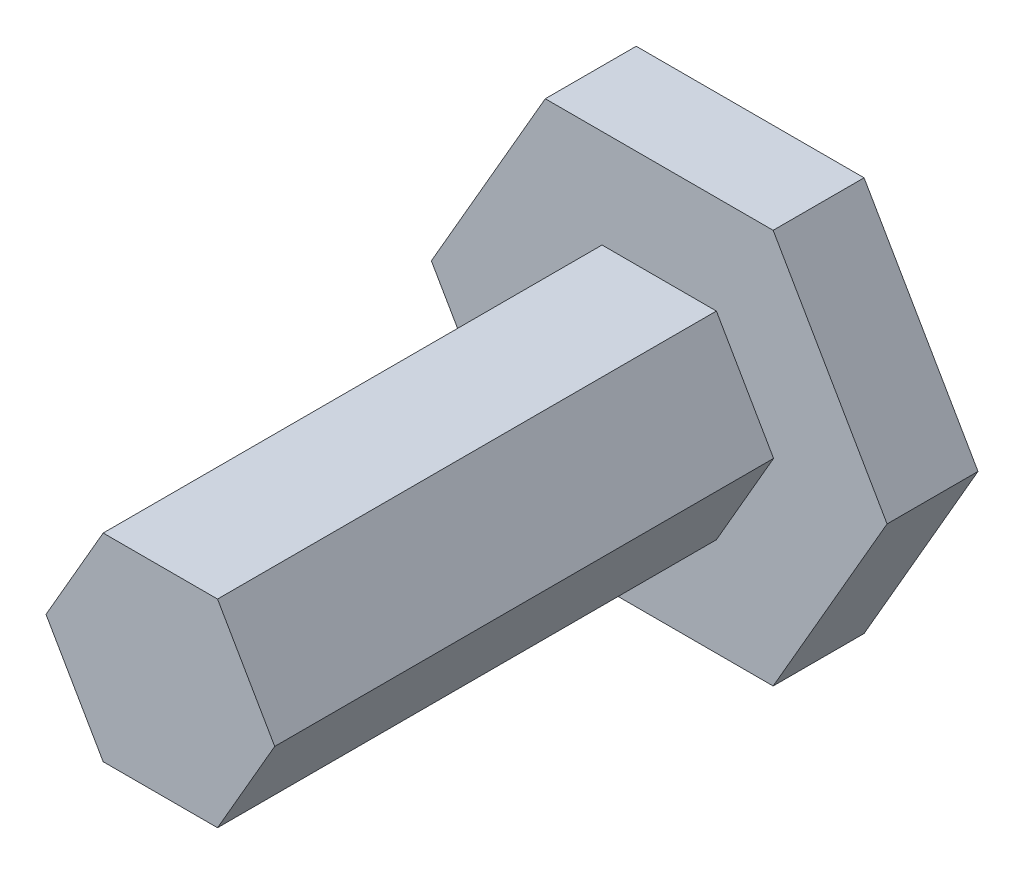
SolidWorks part; units mm, degrees
ref_plane "Front Plane" through (0, 0, 0) normal (0, 0, 1) x (1, 0, 0)
ref_plane "Top Plane" through (0, 0, 0) normal (0, 1, 0) x (1, 0, 0)
ref_plane "Right Plane" through (0, 0, 0) normal (1, 0, 0) x (0, 0, -1)
sketch "Sketch1" plane through (0, 0, 0) normal (0, 0, 1) x (1, 0, 0)
  line L0 (2.4047, -4.1651) -> (4.8094, 0)
  line L1 (1.25, -2.1651) -> (2.5, 0)
  line L2 (2.5, 0) -> (1.25, 2.1651)
  line L3 (1.25, 2.1651) -> (-1.25, 2.1651)
  line L4 (-1.25, 2.1651) -> (-2.5, 0)
  line L5 (-2.5, 0) -> (-1.25, -2.1651)
  line L6 (-1.25, -2.1651) -> (1.25, -2.1651)
  line L7 (4.8094, 0) -> (2.4047, 4.1651)
  line L8 (2.4047, 4.1651) -> (-2.4047, 4.1651)
  line L9 (-2.4047, 4.1651) -> (-4.8094, 0)
  line L10 (-4.8094, 0) -> (-2.4047, -4.1651)
  line L11 (-2.4047, -4.1651) -> (2.4047, -4.1651)
  circle A0 centre (0, 0) radius 2.1651 construction
  dimension "D2" = 2.5
  dimension "D1" = 2
extrude "Boss-Extrude1" add sketch "Sketch1" along normal blind 10 contours L5 L6 L1 L2 L3 L4 region at (0, 0, 0)
extrude "Boss-Extrude2" add sketch "Sketch1<3>" against normal blind 2 contours L5 L6 L1 L2 L3 L4 | L10 L11 L0 L7 L8 L9 L6 L5 L4 L3 L2 L1 region at (0, -4.0378, 0) region at (0, 0, 0)
sketch "Sketch1<3>" plane through (0, 0, 0) normal (0, 0, 1) x (1, 0, 0) same geometry as "Sketch1"
other "Move Face1" flip direction yes face at (0, 0, 0) face at (0, 4.1651, -1) face at (3.6071, 2.0825, -1) face at (3.6071, -2.0825, -1) face at (0, -4.1651, -1) face at (-3.6071, 2.0825, -1) face at (-3.6071, -2.0825, -1) face at (1.875, 1.0825, 5) face at (0, 2.1651, 5) face at (-1.875, 1.0825, 5) face at (-1.875, -1.0825, 5) face at (0, -2.1651, 5) face at (1.875, -1.0825, 5) offset 0.15 parameters "D1"=0.15
equation "\"D1@Boss-Extrude1\"= 5 + 5"
